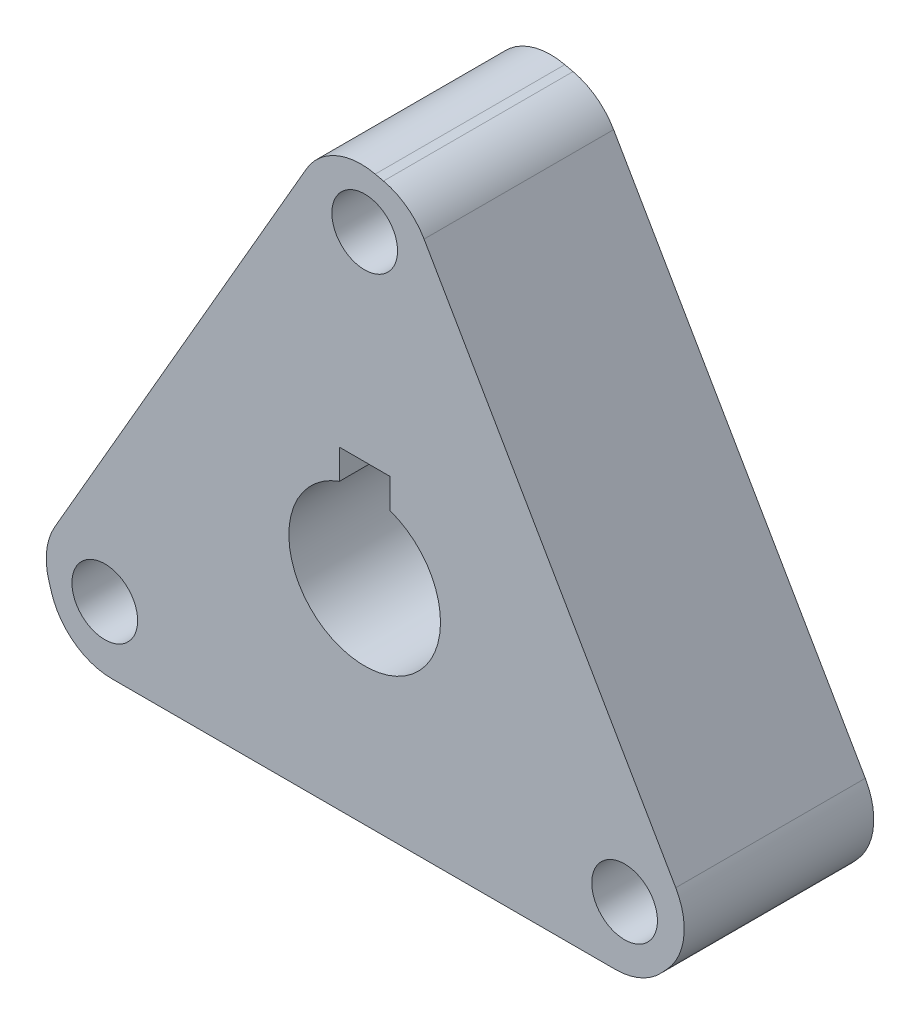
SolidWorks part; units mm, degrees
ref_plane "正面" through (0, 0, 0) normal (0, 0, 1) x (1, 0, 0)
ref_plane "平面" through (0, 0, 0) normal (0, 1, 0) x (1, 0, 0)
ref_plane "右側面" through (0, 0, 0) normal (1, 0, 0) x (0, 0, -1)
sketch "ｽｹｯﾁ1" plane through (0, 0, 0) normal (0, 0, 1) x (1, 0, 0)
  line L0 (0, 0) -> (-20.5681, -11.875) construction
  line L1 (0, 23.75) -> (-20.5681, -11.875) construction
  line L2 (-20.5681, -11.875) -> (20.5681, -11.875) construction
  line L3 (20.5681, -11.875) -> (0, 23.75) construction
  line L4 (-4.6132, 25.7596) -> (-24.5285, -8.7346)
  line L5 (-20.0019, -16.875) -> (19.8287, -16.875)
  line L6 (24.6151, -8.8846) -> (4.6999, 25.6096)
  line L7 (0, 33.75) -> (-29.2284, -16.875) construction
  line L8 (29.2284, -16.875) -> (0, 33.75) construction
  line L9 (1.4894, 27.9826) -> (0.8365, 28.1326)
  line L10 (-29.2284, -16.875) -> (29.2284, -16.875) construction
  line L11 (-24.9784, -12.7015) -> (-24.7818, -13.3419)
  line L12 (23.489, -15.2812) -> (23.9453, -14.7908)
  line L14 (-2, 4) -> (2, 4)
  line L15 (-2, 4) -> (-2, 8)
  line L16 (-2, 8) -> (2, 8)
  line L17 (2, 4) -> (2, 8)
  line L18 (-2, 4) -> (2, 8) construction
  line L19 (-2, 8) -> (2, 4) construction
  circle A0 centre (0, 0) radius 11.875 construction
  circle A1 centre (0, 23.75) radius 2.6
  circle A2 centre (20.5681, -11.875) radius 2.6
  circle A3 centre (-20.5681, -11.875) radius 2.6
  circle A4 centre (0, 0) radius 6
  arc A5 (-24.9784, -12.7015) -> (-24.5285, -8.7346) centre (-20.1984, -11.2346) cw
  arc A6 (-24.7818, -13.3419) -> (-20.0019, -16.875) centre (-20.0019, -11.875) ccw
  arc A7 (23.489, -15.2812) -> (19.8287, -16.875) centre (19.8287, -11.875) cw
  arc A8 (23.9453, -14.7908) -> (24.6151, -8.8846) centre (20.285, -11.3846) ccw
  arc A9 (1.4894, 27.9826) -> (4.6999, 25.6096) centre (0.3697, 23.1096) cw
  arc A10 (0.8365, 28.1326) -> (-4.6132, 25.7596) centre (-0.2831, 23.2596) ccw
  point P31 (0, 6)
  dimension "D1" = 5.2
  dimension "D2" = 5.2
  dimension "D3" = 5.2
  dimension "D5" = 12
  dimension "D7" = 5
  dimension "D4" = 23.75
  dimension "D8" = 4
  dimension "D9" = 4
  dimension "D6" = 5
extrude "ﾎﾞｽ - 押し出し1" add sketch "ｽｹｯﾁ1" along normal blind 15 contours L9 A10 L4 A5 L11 A6 L5 A7 L12 A8 L6 A9 A1 A2 A3 A4 L15 L16 L17 region at (-2.0089, 27.223, 0)
sketch "ｽｹｯﾁ3" plane through (0, -16.875, 0) normal (0, -1, 0) x (1, 0, 0)
  line L0 (-20.0019, 0) -> (19.8287, 0) construction
  circle A0 centre (0, 5) radius 1.5
  dimension "D1" = 5
  dimension "D2" = 3
extrude "ｶｯﾄ - 押し出し1" cut sketch "ｽｹｯﾁ3" against normal up to next
sketch "ｽｹｯﾁ4" plane through (0, -16.875, 0) normal (0, -1, 0) x (1, 0, 0)
  circle A0 centre (0, 5) radius 3.1
  dimension "D1" = 6.2
extrude "ｶｯﾄ - 押し出し2" cut sketch "ｽｹｯﾁ4" against normal blind 3
sketch "ｽｹｯﾁ5" plane through (0, 0, 0) normal (0, 0, -1) x (-1, 0, 0)
  line L12 (0, 19.75) -> (-17.104, -9.875)
  line L13 (-17.104, -9.875) -> (17.104, -9.875)
  line L14 (17.104, -9.875) -> (0, 19.75)
  line L15 (0, 19.75) -> (-17.104, -9.875)
  line L16 (-17.104, -9.875) -> (17.104, -9.875)
  line L17 (17.104, -9.875) -> (0, 19.75)
  circle A12 centre (0, 23.75) radius 7.6
  circle A13 centre (0, 23.75) radius 7.6
  circle A15 centre (-20.5681, -11.875) radius 7.6
  circle A16 centre (-20.5681, -11.875) radius 7.6
  circle A18 centre (20.5681, -11.875) radius 7.6
  circle A19 centre (20.5681, -11.875) radius 7.6
  circle A20 centre (0, 0) radius 11
  dimension "D4" = 22
  dimension "D1" = 5
  dimension "D2" = 5
  dimension "D3" = 5
  dimension "D5" = 7
extrude "ｶｯﾄ - 押し出し3" cut sketch "ｽｹｯﾁ5" against normal blind 10 contours A20 L15 A16 L16 | A20 L17 A13 L15 | A20 L16 A19 L17 region at (0, 12.8976, 0) region at (11.1697, -6.4488, 0) region at (-11.1697, -6.4488, 0)
